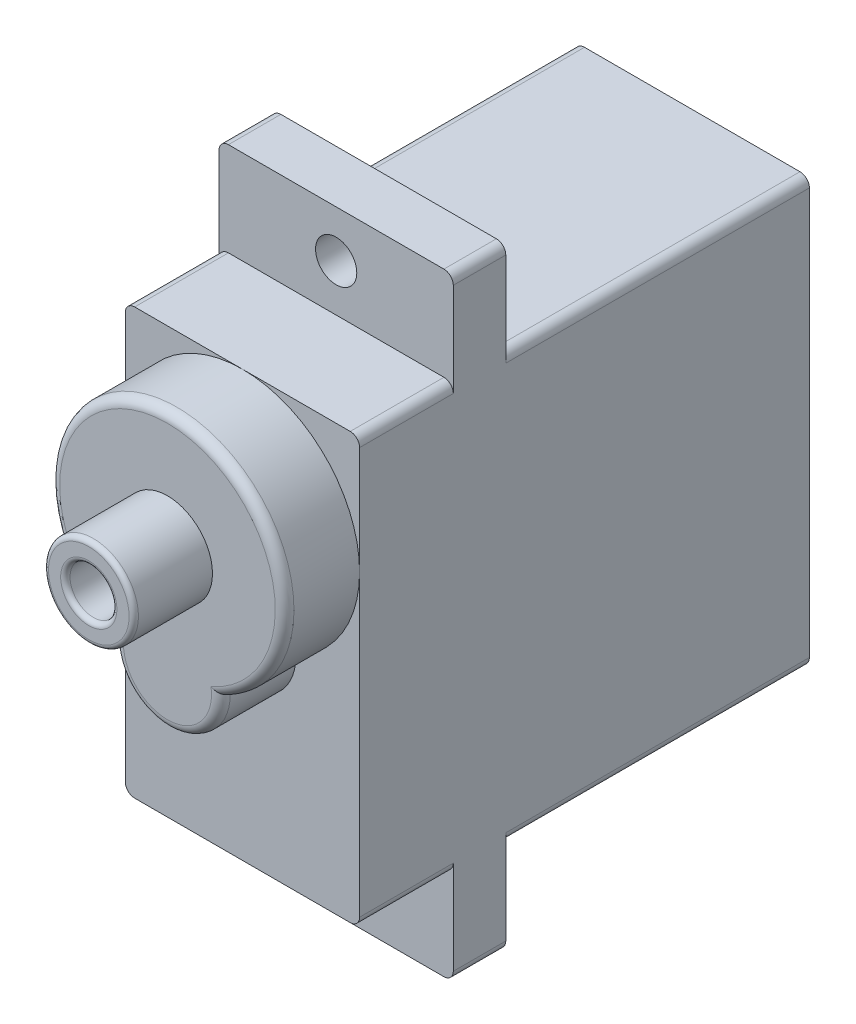
SolidWorks part; units mm, degrees
ref_plane "Спереди (Плоскость XY)" through (0, 0, 0) normal (0, 0, 1) x (1, 0, 0)
ref_plane "Сверху (Плоскость XZ)" through (0, 0, 0) normal (0, 1, 0) x (1, 0, 0)
ref_plane "Справа (Плоскость ZY)" through (0, 0, 0) normal (1, 0, 0) x (0, 0, -1)
sketch "Эскиз1" plane through (0, 0, 0) normal (0, 0, 1) x (1, 0, 0)
  line L1 (-6.25, 11.35) -> (6.25, 11.35)
  line L2 (-6.25, 11.35) -> (-6.25, -11.35)
  line L3 (-6.25, -11.35) -> (6.25, -11.35)
  line L4 (6.25, 11.35) -> (6.25, -11.35)
  line L5 (-6.25, 11.35) -> (6.25, -11.35) construction
  line L6 (-6.25, -11.35) -> (6.25, 11.35) construction
  point P0 (0, 0)
  dimension "D1" = 22.7
  dimension "D2" = 12.5
extrude "Бобышка-Вытянуть1" add sketch "Эскиз1" along normal blind 24
ref_plane "Плоскость1" through (0, 0, 19) normal (0, 0, 1) x (1, 0, 0)
sketch "Эскиз2" plane through (0, 0, 19) normal (0, 0, 1) x (1, 0, 0)
  line L0 (6.25, -11.35) -> (6.25, 11.35) construction
  line L1 (-6.25, 11.35) -> (6.25, 11.35)
  line L2 (-6.25, 11.35) -> (-6.25, 16.35)
  line L3 (-6.25, 16.35) -> (6.25, 16.35)
  line L4 (6.25, 11.35) -> (6.25, 16.35)
  line L5 (0, 0) -> (10.6869, 0) construction
  line L6 (6.25, -11.35) -> (6.25, -16.35)
  line L7 (-6.25, -16.35) -> (6.25, -16.35)
  line L8 (-6.25, -11.35) -> (-6.25, -16.35)
  line L9 (-6.25, -11.35) -> (6.25, -11.35)
  dimension "D1" = 5
extrude "Бобышка-Вытянуть2" add sketch "Эскиз2" against normal blind 2.8
sketch "Эскиз3" plane through (0, 0, 19) normal (0, 0, 1) x (1, 0, 0)
  line L0 (0, 0) -> (0, 50000) construction
  line L1 (0, 0) -> (10.3846, 0) construction
  line L2 (6.25, 16.35) -> (-6.25, 16.35) construction
  circle A0 centre (0, 13.85) radius 1.1
  circle A1 centre (0, -13.85) radius 1.1
  dimension "D1" = 2.2
  dimension "D2" = 2.5
extrude "Вырез-Вытянуть1" cut sketch "Эскиз3" against normal blind 2.8
fillet "Скругление1" radius 0.5 12 edges at (-6.25, -11.35, 8.1) (-6.25, -16.35, 17.6) (-6.25, -11.35, 21.5) (6.25, -11.35, 21.5) (6.25, -16.35, 17.6) (6.25, -11.35, 8.1) (6.25, 16.35, 17.6) (-6.25, 16.35, 17.6) (-6.25, 11.35, 8.1) (-6.25, 11.35, 21.5) (6.25, 11.35, 21.5) (6.25, 11.35, 8.1)
sketch "Эскиз4" plane through (0, 0, 24) normal (0, 0, 1) x (1, 0, 0)
  line L0 (6.25, -10.85) -> (6.25, 10.85) construction
  line L1 (5.75, 11.35) -> (-5.75, 11.35) construction
  circle A0 centre (0, 5.1) radius 6.25
extrude "Бобышка-Вытянуть3" add sketch "Эскиз4" along normal blind 4
sketch "Эскиз5" plane through (0, 0, 28) normal (0, 0, 1) x (1, 0, 0)
  line L0 (-5.75, 11.35) -> (5.75, 11.35) construction
  circle A0 centre (0, -0.5) radius 2.85
  dimension "D1" = 5.7
  dimension "D2" = 14.7
extrude "Бобышка-Вытянуть4" add sketch "Эскиз5" against normal blind 5.8
fillet "Скругление2" radius 0.5 2 edges at (0, -3.35, 28) (0, 11.35, 28)
sketch "Эскиз6" plane through (0, 0, 28) normal (0, 0, 1) x (1, 0, 0)
  circle A0 centre (0, 5.1) radius 2.4
  dimension "D1" = 4.8
extrude "Бобышка-Вытянуть5" add sketch "Эскиз6" along normal blind 4.2
sketch "Эскиз7" plane through (0, 0, 32.2) normal (0, 0, 1) x (1, 0, 0)
  circle A0 centre (0, 5.1) radius 1.25
  dimension "D1" = 2.5
extrude "Вырез-Вытянуть2" cut sketch "Эскиз7" against normal blind 4.2
fillet "Скругление3" radius 0.25 2 edges at (2.4, 5.1, 32.2) (1.25, 5.1, 32.2)
